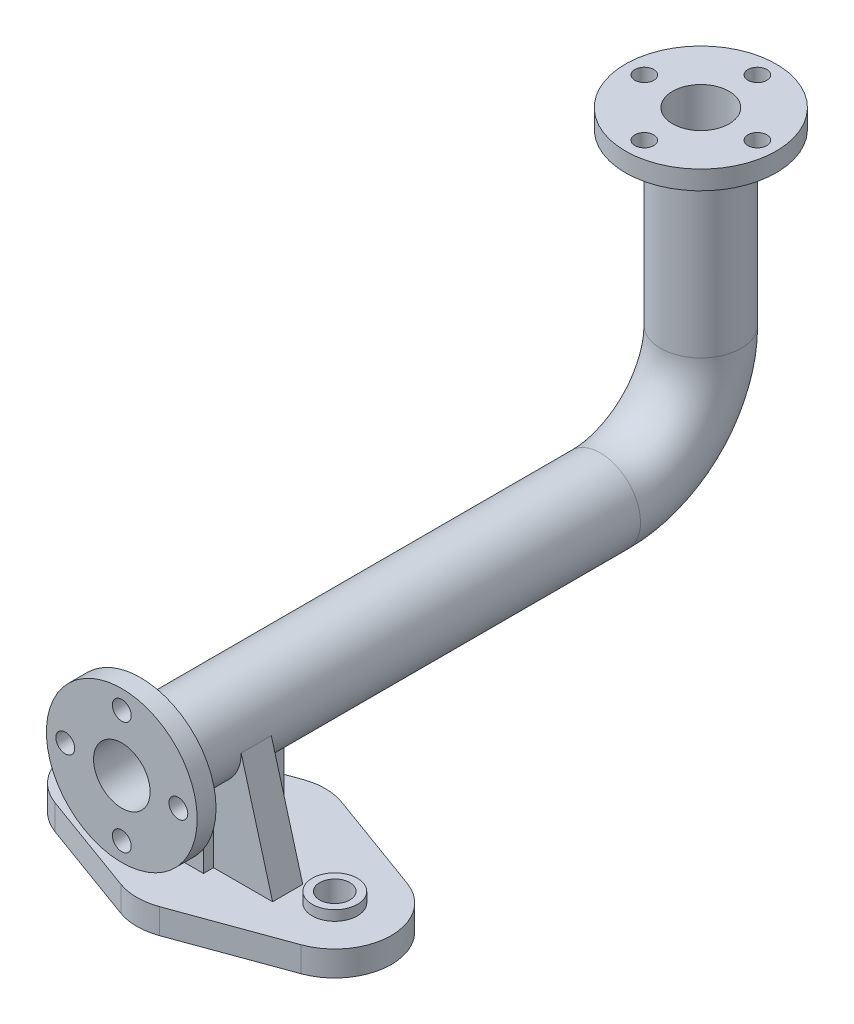
SolidWorks part; units mm, degrees
ref_plane "Front Plane" through (0, 0, 0) normal (0, 0, 1) x (1, 0, 0)
ref_plane "Top Plane" through (0, 0, 0) normal (0, 1, 0) x (1, 0, 0)
ref_plane "Right Plane" through (0, 0, 0) normal (1, 0, 0) x (0, 0, -1)
sketch "Sketch1" plane through (0, 0, 0) normal (1, 0, 0) x (0, 0, -1)
  line L0 (0, 0) -> (0, -135)
  line L1 (-80, -215) -> (-445.82, -215)
  arc A0 (0, -135) -> (-80, -215) centre (-80, -135) cw
  point P6 (0, -215)
  dimension "D2" = 80
  dimension "D1" = 215
  dimension "D3" = 365.82
sweep "Sweep-Thin1" add path "Sketch1" circular profile diameter 64 parameters "D1"=9.5, "D3"=64
sketch "Sketch16" plane through (0, 0, 0) normal (0, 1, 0) x (1, 0, 0)
  circle A0 centre (0, 0) radius 45 construction
  circle A1 centre (0, 0) radius 60
  circle A2 centre (0, -45) radius 7.5
  circle A3 centre (-45, 0) radius 7.5
  circle A4 centre (0, 45) radius 7.5
  circle A5 centre (45, 0) radius 7.5
  circle A8 centre (0, 0) radius 22.5 construction
  circle A9 centre (0, 0) radius 22.5
  point P15 (0, 0)
  dimension "D1" = 120
  dimension "D2" = 90
  dimension "D3" = 15
  dimension "D4" = 4
extrude "Boss-Extrude1" add sketch "Sketch16" along normal blind 15
sketch "Sketch17" plane through (0, 0, 445.82) normal (0, 0, 1) x (1, 0, 0)
  circle A2 centre (0, -215) radius 45 construction
  circle A5 centre (0, -215) radius 22.5 construction
  circle A6 centre (0, -215) radius 22.5
  circle A7 centre (0, -215) radius 60
  circle A8 centre (0, -260) radius 7.5
  circle A9 centre (-45, -215) radius 7.5
  circle A10 centre (45, -215) radius 7.5
  circle A11 centre (0, -170) radius 7.5
  dimension "D1" = 90
  dimension "D2" = 120
  dimension "D3" = 15
extrude "Boss-Extrude2" add sketch "Sketch17" along normal blind 15
ref_plane "Plane1" through (0, -325, 0) normal (0, 1, 0) x (1, 0, 0)
sketch "Sketch24" plane through (0, -325, 0) normal (0, 1, 0) x (1, 0, 0)
  line L0 (0, -460.82) -> (0, -373.82) construction
  line L1 (-60, -460.82) -> (60, -460.82) construction
  line L2 (-82.5, -373.82) -> (82.5, -373.82) construction
  line L3 (15.3909, -446.1337) -> (97.8909, -416.1062)
  line L4 (97.8909, -331.5338) -> (15.3909, -301.5063)
  line L5 (0, -295.9045) -> (0, -373.82) construction
  line L6 (-97.8909, -331.5338) -> (-15.3909, -301.5063)
  line L7 (-15.3909, -446.1337) -> (-97.8909, -416.1062)
  line L8 (60, -445.82) -> (-60, -445.82) construction
  arc A0 (97.8909, -416.1062) -> (97.8909, -331.5338) centre (82.5, -373.82) ccw
  arc A1 (-97.8909, -416.1062) -> (-97.8909, -331.5338) centre (-82.5, -373.82) cw
  arc A2 (15.3909, -446.1337) -> (-15.3909, -446.1337) centre (0, -403.8475) cw
  arc A3 (15.3909, -301.5063) -> (-15.3909, -301.5063) centre (0, -343.7925) ccw
  circle A4 centre (-82.5, -373.82) radius 12
  circle A5 centre (82.5, -373.82) radius 12
  point P18 (0, -451.7355)
  dimension "D1" = 45
  dimension "D2" = 165
  dimension "D3" = 45
  dimension "D6" = 24
  dimension "D4" = 72
  dimension "D5" = 40
extrude "Boss-Extrude3" add sketch "Sketch24" along normal blind 20 separate body
sketch "Sketch26" plane through (0, -305, 0) normal (0, 1, 0) x (1, 0, 0)
  line L0 (0, -341.82) -> (0, -405.82)
  line L2 (60, -445.82) -> (-60, -445.82) construction
  point P3 (0, -373.82)
  dimension "D1" = 64
  dimension "D2" = 72
extrude "Extrude-Thin1" add sketch "Sketch26" along normal up to next thin thin type mid plane wall 20
ref_plane "Plane2" through (0, 0, 385.82) normal (0, 0, -1) x (-1, 0, 0)
sketch "Sketch27" plane through (0, 0, 385.82) normal (0, 0, -1) x (-1, 0, 0)
  line L0 (-57, -305) -> (-32, -215)
  line L1 (-97.8909, -305) -> (-15.3909, -305) construction
  line L2 (0, -325) -> (0, -281.826) construction
  line L3 (-15.3909, -325) -> (15.3909, -325) construction
  circle A0 centre (0, -215) radius 32 construction
  point P11 (0, 0)
  point P12 (-32, -215)
  dimension "D1" = 114
rib "Rib1" sketch "Sketch27" sketch "Sketch27" thickness 24 extrusion direction parallel to sketch draft on no parameters "D1"=24
mirror "Mirror3" about plane through (0, 0, 0) normal (1, 0, 0) of "Rib1"
sketch "Sketch28" plane through (0, -305, 0) normal (0, 1, 0) x (1, 0, 0)
  circle A0 centre (82.5, -373.82) radius 12 construction
  circle A1 centre (82.5, -373.82) radius 12
  circle A2 centre (-82.5, -373.82) radius 12 construction
  circle A3 centre (-82.5, -373.82) radius 12
  circle A4 centre (-82.5, -373.82) radius 18
  circle A5 centre (82.5, -373.82) radius 18
  dimension "D1" = 36
extrude "Boss-Extrude4" add sketch "Sketch28" along normal blind 8
